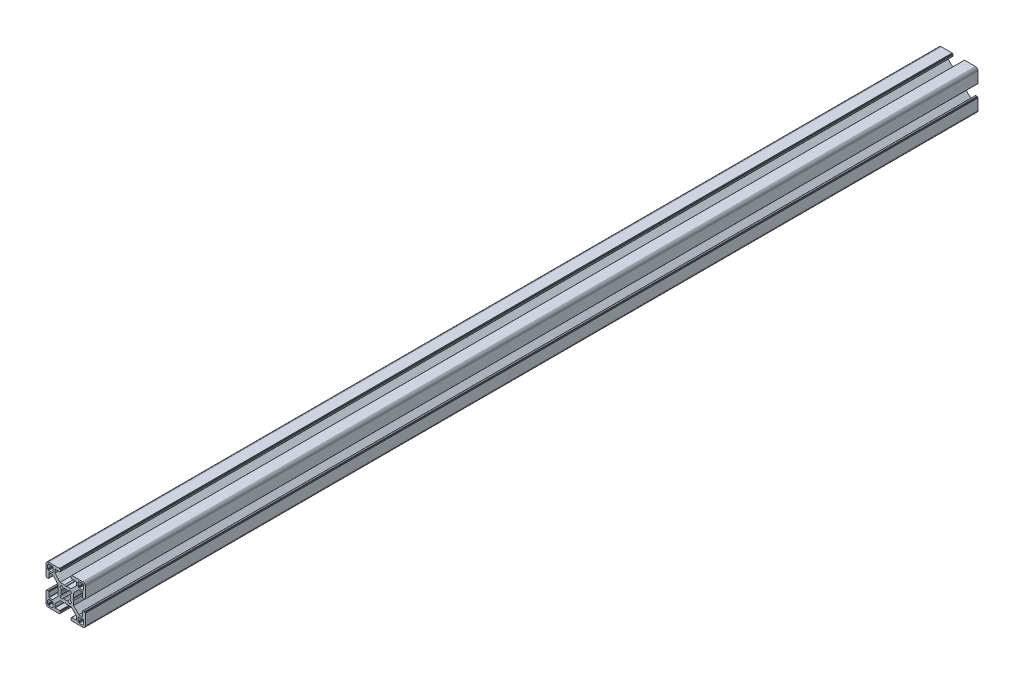
SolidWorks part; units mm, degrees
ref_plane "Front Plane" through (0, 0, 0) normal (0, 0, 1) x (1, 0, 0)
ref_plane "Top Plane" through (0, 0, 0) normal (0, 1, 0) x (1, 0, 0)
ref_plane "Right Plane" through (0, 0, 0) normal (1, 0, 0) x (0, 0, -1)
ref_plane "Plane1" through (0, 0, 0) normal (0, 0, 1) x (1, 0, 0)
sketch "Sketch1" plane through (0, 0, 0) normal (0, 0, 1) x (1, 0, 0)
  line L0 (28.3473, 29.9696) -> (28, 30)
  line L1 (28, 30) -> (19.75, 30)
  line L2 (19.75, 30) -> (19.7153, 29.997)
  line L3 (19.7153, 29.997) -> (19.6816, 29.9879)
  line L4 (19.6816, 29.9879) -> (19.65, 29.9732)
  line L5 (19.65, 29.9732) -> (19.6214, 29.9532)
  line L6 (19.6214, 29.9532) -> (19.5968, 29.9286)
  line L7 (19.5968, 29.9286) -> (19.5768, 29.9)
  line L8 (19.5768, 29.9) -> (19.5621, 29.8684)
  line L9 (19.5621, 29.8684) -> (19.553, 29.8347)
  line L10 (19.553, 29.8347) -> (19.55, 29.8)
  line L11 (19.55, 29.8) -> (19.55, 29.7)
  line L12 (19.55, 29.7) -> (19.547, 29.6653)
  line L13 (19.547, 29.6653) -> (19.5379, 29.6316)
  line L14 (19.5379, 29.6316) -> (19.5232, 29.6)
  line L15 (19.5232, 29.6) -> (19.5032, 29.5714)
  line L16 (19.5032, 29.5714) -> (19.4786, 29.5468)
  line L17 (19.4786, 29.5468) -> (19.45, 29.5268)
  line L18 (19.45, 29.5268) -> (19.4184, 29.5121)
  line L19 (19.4184, 29.5121) -> (19.3847, 29.503)
  line L20 (19.3847, 29.503) -> (19.35, 29.5)
  line L21 (19.35, 29.5) -> (19.25, 29.5)
  line L22 (19.25, 29.5) -> (19.2153, 29.497)
  line L23 (19.2153, 29.497) -> (19.1816, 29.4879)
  line L24 (19.1816, 29.4879) -> (19.15, 29.4732)
  line L25 (19.15, 29.4732) -> (19.1214, 29.4532)
  line L26 (19.1214, 29.4532) -> (19.0968, 29.4286)
  line L27 (19.0968, 29.4286) -> (19.0768, 29.4)
  line L28 (19.0768, 29.4) -> (19.0621, 29.3684)
  line L29 (19.0621, 29.3684) -> (19.053, 29.3347)
  line L30 (19.053, 29.3347) -> (19.05, 29.3)
  line L31 (19.05, 29.3) -> (19.05, 28.4)
  line L32 (19.05, 28.4) -> (19.0591, 28.2958)
  line L33 (19.0591, 28.2958) -> (19.0862, 28.1948)
  line L34 (19.0862, 28.1948) -> (19.1304, 28.1)
  line L35 (19.1304, 28.1) -> (19.1904, 28.0143)
  line L36 (19.1904, 28.0143) -> (19.2643, 27.9404)
  line L37 (19.2643, 27.9404) -> (19.35, 27.8804)
  line L38 (19.35, 27.8804) -> (19.4448, 27.8362)
  line L39 (19.4448, 27.8362) -> (19.5458, 27.8091)
  line L40 (19.5458, 27.8091) -> (19.65, 27.8)
  line L41 (19.65, 27.8) -> (23.05, 27.8)
  line L42 (23.05, 27.8) -> (23.0847, 27.7969)
  line L43 (23.0847, 27.7969) -> (23.1184, 27.7879)
  line L44 (23.1184, 27.7879) -> (23.15, 27.7732)
  line L45 (23.15, 27.7732) -> (23.1786, 27.7532)
  line L46 (23.1786, 27.7532) -> (23.2032, 27.7285)
  line L47 (23.2032, 27.7285) -> (23.2232, 27.7)
  line L48 (23.2232, 27.7) -> (23.2379, 27.6684)
  line L49 (23.2379, 27.6684) -> (23.247, 27.6347)
  line L50 (23.247, 27.6347) -> (23.25, 27.6)
  line L51 (23.25, 27.6) -> (23.25, 25.05)
  line L52 (23.25, 25.05) -> (19.2045, 21)
  line L53 (19.2045, 21) -> (15.9, 21)
  line L54 (15.9, 21) -> (15, 20.4848)
  line L55 (15, 20.4848) -> (14.1, 21)
  line L56 (14.1, 21) -> (10.7955, 21)
  line L57 (10.7955, 21) -> (7.9973, 23.8013)
  line L58 (7.9973, 23.8013) -> (6.75, 25.05)
  line L59 (6.75, 25.05) -> (6.75, 27.6)
  line L60 (6.75, 27.6) -> (6.753, 27.6347)
  line L61 (6.753, 27.6347) -> (6.7621, 27.6684)
  line L62 (6.7621, 27.6684) -> (6.7768, 27.7)
  line L63 (6.7768, 27.7) -> (6.7968, 27.7285)
  line L64 (6.7968, 27.7285) -> (6.8215, 27.7532)
  line L65 (6.8215, 27.7532) -> (6.85, 27.7732)
  line L66 (6.85, 27.7732) -> (6.8816, 27.7879)
  line L67 (6.8816, 27.7879) -> (6.9153, 27.7969)
  line L68 (6.9153, 27.7969) -> (6.95, 27.8)
  line L69 (6.95, 27.8) -> (10.35, 27.8)
  line L70 (10.35, 27.8) -> (10.4542, 27.8091)
  line L71 (10.4542, 27.8091) -> (10.5552, 27.8362)
  line L72 (10.5552, 27.8362) -> (10.65, 27.8804)
  line L73 (10.65, 27.8804) -> (10.7357, 27.9404)
  line L74 (10.7357, 27.9404) -> (10.8096, 28.0143)
  line L75 (10.8096, 28.0143) -> (10.8696, 28.1)
  line L76 (10.8696, 28.1) -> (10.9138, 28.1948)
  line L77 (10.9138, 28.1948) -> (10.9409, 28.2958)
  line L78 (10.9409, 28.2958) -> (10.95, 28.4)
  line L79 (10.95, 28.4) -> (10.95, 29.3)
  line L80 (10.95, 29.3) -> (10.947, 29.3347)
  line L81 (10.947, 29.3347) -> (10.938, 29.3684)
  line L82 (10.938, 29.3684) -> (10.9232, 29.4)
  line L83 (10.9232, 29.4) -> (10.9032, 29.4286)
  line L84 (10.9032, 29.4286) -> (10.8786, 29.4532)
  line L85 (10.8786, 29.4532) -> (10.85, 29.4732)
  line L86 (10.85, 29.4732) -> (10.8184, 29.4879)
  line L87 (10.8184, 29.4879) -> (10.7847, 29.497)
  line L88 (10.7847, 29.497) -> (10.75, 29.5)
  line L89 (10.75, 29.5) -> (10.65, 29.5)
  line L90 (10.65, 29.5) -> (10.6153, 29.503)
  line L91 (10.6153, 29.503) -> (10.5816, 29.5121)
  line L92 (10.5816, 29.5121) -> (10.55, 29.5268)
  line L93 (10.55, 29.5268) -> (10.5214, 29.5468)
  line L94 (10.5214, 29.5468) -> (10.4968, 29.5714)
  line L95 (10.4968, 29.5714) -> (10.4768, 29.6)
  line L96 (10.4768, 29.6) -> (10.4621, 29.6316)
  line L97 (10.4621, 29.6316) -> (10.453, 29.6653)
  line L98 (10.453, 29.6653) -> (10.45, 29.7)
  line L99 (10.45, 29.7) -> (10.45, 29.8)
  line L100 (10.45, 29.8) -> (10.447, 29.8347)
  line L101 (10.447, 29.8347) -> (10.4379, 29.8684)
  line L102 (10.4379, 29.8684) -> (10.4232, 29.9)
  line L103 (10.4232, 29.9) -> (10.4032, 29.9286)
  line L104 (10.4032, 29.9286) -> (10.3786, 29.9532)
  line L105 (10.3786, 29.9532) -> (10.35, 29.9732)
  line L106 (10.35, 29.9732) -> (10.3184, 29.9879)
  line L107 (10.3184, 29.9879) -> (10.2847, 29.997)
  line L108 (10.2847, 29.997) -> (10.25, 30)
  line L109 (10.25, 30) -> (2, 30)
  line L110 (2, 30) -> (1.6527, 29.9696)
  line L111 (1.6527, 29.9696) -> (1.316, 29.8794)
  line L112 (1.316, 29.8794) -> (1, 29.7321)
  line L113 (1, 29.7321) -> (0.7144, 29.5321)
  line L114 (0.7144, 29.5321) -> (0.4679, 29.2856)
  line L115 (0.4679, 29.2856) -> (0.2679, 29)
  line L116 (0.2679, 29) -> (0.1206, 28.684)
  line L117 (0.1206, 28.684) -> (0.0304, 28.3473)
  line L118 (0.0304, 28.3473) -> (0, 28)
  line L119 (0, 28) -> (0, 19.75)
  line L120 (0, 19.75) -> (0.003, 19.7153)
  line L121 (0.003, 19.7153) -> (0.0121, 19.6816)
  line L122 (0.0121, 19.6816) -> (0.0268, 19.65)
  line L123 (0.0268, 19.65) -> (0.0468, 19.6214)
  line L124 (0.0468, 19.6214) -> (0.0714, 19.5968)
  line L125 (0.0714, 19.5968) -> (0.1, 19.5768)
  line L126 (0.1, 19.5768) -> (0.1316, 19.5621)
  line L127 (0.1316, 19.5621) -> (0.1653, 19.553)
  line L128 (0.1653, 19.553) -> (0.2, 19.55)
  line L129 (0.2, 19.55) -> (0.3, 19.55)
  line L130 (0.3, 19.55) -> (0.3347, 19.547)
  line L131 (0.3347, 19.547) -> (0.3684, 19.5379)
  line L132 (0.3684, 19.5379) -> (0.4, 19.5232)
  line L133 (0.4, 19.5232) -> (0.4286, 19.5032)
  line L134 (0.4286, 19.5032) -> (0.4532, 19.4786)
  line L135 (0.4532, 19.4786) -> (0.4732, 19.45)
  line L136 (0.4732, 19.45) -> (0.4879, 19.4184)
  line L137 (0.4879, 19.4184) -> (0.497, 19.3847)
  line L138 (0.497, 19.3847) -> (0.5, 19.35)
  line L139 (0.5, 19.35) -> (0.5, 19.25)
  line L140 (0.5, 19.25) -> (0.503, 19.2153)
  line L141 (0.503, 19.2153) -> (0.5121, 19.1816)
  line L142 (0.5121, 19.1816) -> (0.5268, 19.15)
  line L143 (0.5268, 19.15) -> (0.5468, 19.1214)
  line L144 (0.5468, 19.1214) -> (0.5714, 19.0968)
  line L145 (0.5714, 19.0968) -> (0.6, 19.0768)
  line L146 (0.6, 19.0768) -> (0.6316, 19.0621)
  line L147 (0.6316, 19.0621) -> (0.6653, 19.053)
  line L148 (0.6653, 19.053) -> (0.7, 19.05)
  line L149 (0.7, 19.05) -> (1.6, 19.05)
  line L150 (1.6, 19.05) -> (1.7042, 19.0591)
  line L151 (1.7042, 19.0591) -> (1.8052, 19.0862)
  line L152 (1.8052, 19.0862) -> (1.9, 19.1304)
  line L153 (1.9, 19.1304) -> (1.9857, 19.1904)
  line L154 (1.9857, 19.1904) -> (2.0596, 19.2643)
  line L155 (2.0596, 19.2643) -> (2.1196, 19.35)
  line L156 (2.1196, 19.35) -> (2.1638, 19.4448)
  line L157 (2.1638, 19.4448) -> (2.1909, 19.5458)
  line L158 (2.1909, 19.5458) -> (2.2, 19.65)
  line L159 (2.2, 19.65) -> (2.2, 23.05)
  line L160 (2.2, 23.05) -> (2.203, 23.0847)
  line L161 (2.203, 23.0847) -> (2.2121, 23.1184)
  line L162 (2.2121, 23.1184) -> (2.2268, 23.15)
  line L163 (2.2268, 23.15) -> (2.2468, 23.1786)
  line L164 (2.2468, 23.1786) -> (2.2714, 23.2032)
  line L165 (2.2714, 23.2032) -> (2.3, 23.2232)
  line L166 (2.3, 23.2232) -> (2.3316, 23.2379)
  line L167 (2.3316, 23.2379) -> (2.3653, 23.247)
  line L168 (2.3653, 23.247) -> (2.4, 23.25)
  line L169 (2.4, 23.25) -> (4.95, 23.25)
  line L170 (4.95, 23.25) -> (7.9973, 20.2027)
  line L171 (7.9973, 20.2027) -> (8.9955, 19.2045)
  line L172 (8.9955, 19.2045) -> (8.9955, 15.9)
  line L173 (8.9955, 15.9) -> (9.5151, 15)
  line L174 (9.5151, 15) -> (8.9955, 14.1)
  line L175 (8.9955, 14.1) -> (8.9955, 10.7955)
  line L176 (8.9955, 10.7955) -> (4.95, 6.75)
  line L177 (4.95, 6.75) -> (2.4, 6.75)
  line L178 (2.4, 6.75) -> (2.3653, 6.753)
  line L179 (2.3653, 6.753) -> (2.3316, 6.7621)
  line L180 (2.3316, 6.7621) -> (2.3, 6.7768)
  line L181 (2.3, 6.7768) -> (2.2714, 6.7968)
  line L182 (2.2714, 6.7968) -> (2.2468, 6.8214)
  line L183 (2.2468, 6.8214) -> (2.2268, 6.85)
  line L184 (2.2268, 6.85) -> (2.2121, 6.8816)
  line L185 (2.2121, 6.8816) -> (2.203, 6.9153)
  line L186 (2.203, 6.9153) -> (2.2, 6.95)
  line L187 (2.2, 6.95) -> (2.2, 10.35)
  line L188 (2.2, 10.35) -> (2.1909, 10.4542)
  line L189 (2.1909, 10.4542) -> (2.1638, 10.5552)
  line L190 (2.1638, 10.5552) -> (2.1196, 10.65)
  line L191 (2.1196, 10.65) -> (2.0596, 10.7357)
  line L192 (2.0596, 10.7357) -> (1.9857, 10.8096)
  line L193 (1.9857, 10.8096) -> (1.9, 10.8696)
  line L194 (1.9, 10.8696) -> (1.8052, 10.9138)
  line L195 (1.8052, 10.9138) -> (1.7042, 10.9409)
  line L196 (1.7042, 10.9409) -> (1.6, 10.95)
  line L197 (1.6, 10.95) -> (0.7, 10.95)
  line L198 (0.7, 10.95) -> (0.6653, 10.9469)
  line L199 (0.6653, 10.9469) -> (0.6316, 10.9379)
  line L200 (0.6316, 10.9379) -> (0.6, 10.9232)
  line L201 (0.6, 10.9232) -> (0.5715, 10.9032)
  line L202 (0.5715, 10.9032) -> (0.5468, 10.8785)
  line L203 (0.5468, 10.8785) -> (0.5268, 10.85)
  line L204 (0.5268, 10.85) -> (0.5121, 10.8184)
  line L205 (0.5121, 10.8184) -> (0.503, 10.7847)
  line L206 (0.503, 10.7847) -> (0.5, 10.75)
  line L207 (0.5, 10.75) -> (0.5, 10.65)
  line L208 (0.5, 10.65) -> (0.497, 10.6153)
  line L209 (0.497, 10.6153) -> (0.4879, 10.5816)
  line L210 (0.4879, 10.5816) -> (0.4732, 10.55)
  line L211 (0.4732, 10.55) -> (0.4532, 10.5214)
  line L212 (0.4532, 10.5214) -> (0.4286, 10.4968)
  line L213 (0.4286, 10.4968) -> (0.4, 10.4768)
  line L214 (0.4, 10.4768) -> (0.3684, 10.4621)
  line L215 (0.3684, 10.4621) -> (0.3347, 10.453)
  line L216 (0.3347, 10.453) -> (0.3, 10.45)
  line L217 (0.3, 10.45) -> (0.2, 10.45)
  line L218 (0.2, 10.45) -> (0.1653, 10.447)
  line L219 (0.1653, 10.447) -> (0.1316, 10.4379)
  line L220 (0.1316, 10.4379) -> (0.1, 10.4232)
  line L221 (0.1, 10.4232) -> (0.0714, 10.4032)
  line L222 (0.0714, 10.4032) -> (0.0468, 10.3786)
  line L223 (0.0468, 10.3786) -> (0.0268, 10.35)
  line L224 (0.0268, 10.35) -> (0.0121, 10.3184)
  line L225 (0.0121, 10.3184) -> (0.003, 10.2847)
  line L226 (0.003, 10.2847) -> (0, 10.25)
  line L227 (0, 10.25) -> (0, 2)
  line L228 (0, 2) -> (0.0304, 1.6527)
  line L229 (0.0304, 1.6527) -> (0.1206, 1.316)
  line L230 (0.1206, 1.316) -> (0.2679, 1)
  line L231 (0.2679, 1) -> (0.4679, 0.7144)
  line L232 (0.4679, 0.7144) -> (0.7144, 0.4679)
  line L233 (0.7144, 0.4679) -> (1, 0.2679)
  line L234 (1, 0.2679) -> (1.316, 0.1206)
  line L235 (1.316, 0.1206) -> (1.6527, 0.0304)
  line L236 (1.6527, 0.0304) -> (2, 0)
  line L237 (2, 0) -> (10.25, 0)
  line L238 (10.25, 0) -> (10.2847, 0.003)
  line L239 (10.2847, 0.003) -> (10.3184, 0.0121)
  line L240 (10.3184, 0.0121) -> (10.35, 0.0268)
  line L241 (10.35, 0.0268) -> (10.3786, 0.0468)
  line L242 (10.3786, 0.0468) -> (10.4032, 0.0714)
  line L243 (10.4032, 0.0714) -> (10.4232, 0.1)
  line L244 (10.4232, 0.1) -> (10.4379, 0.1316)
  line L245 (10.4379, 0.1316) -> (10.447, 0.1653)
  line L246 (10.447, 0.1653) -> (10.45, 0.2)
  line L247 (10.45, 0.2) -> (10.45, 0.3)
  line L248 (10.45, 0.3) -> (10.453, 0.3347)
  line L249 (10.453, 0.3347) -> (10.4621, 0.3684)
  line L250 (10.4621, 0.3684) -> (10.4768, 0.4)
  line L251 (10.4768, 0.4) -> (10.4968, 0.4286)
  line L252 (10.4968, 0.4286) -> (10.5214, 0.4532)
  line L253 (10.5214, 0.4532) -> (10.55, 0.4732)
  line L254 (10.55, 0.4732) -> (10.5816, 0.4879)
  line L255 (10.5816, 0.4879) -> (10.6153, 0.497)
  line L256 (10.6153, 0.497) -> (10.65, 0.5)
  line L257 (10.65, 0.5) -> (10.75, 0.5)
  line L258 (10.75, 0.5) -> (10.7847, 0.503)
  line L259 (10.7847, 0.503) -> (10.8184, 0.5121)
  line L260 (10.8184, 0.5121) -> (10.85, 0.5268)
  line L261 (10.85, 0.5268) -> (10.8785, 0.5468)
  line L262 (10.8785, 0.5468) -> (10.9032, 0.5715)
  line L263 (10.9032, 0.5715) -> (10.9232, 0.6)
  line L264 (10.9232, 0.6) -> (10.9379, 0.6316)
  line L265 (10.9379, 0.6316) -> (10.9469, 0.6653)
  line L266 (10.9469, 0.6653) -> (10.95, 0.7)
  line L267 (10.95, 0.7) -> (10.95, 1.6)
  line L268 (10.95, 1.6) -> (10.9409, 1.7042)
  line L269 (10.9409, 1.7042) -> (10.9138, 1.8052)
  line L270 (10.9138, 1.8052) -> (10.8696, 1.9)
  line L271 (10.8696, 1.9) -> (10.8096, 1.9857)
  line L272 (10.8096, 1.9857) -> (10.7357, 2.0596)
  line L273 (10.7357, 2.0596) -> (10.65, 2.1196)
  line L274 (10.65, 2.1196) -> (10.5552, 2.1638)
  line L275 (10.5552, 2.1638) -> (10.4542, 2.1909)
  line L276 (10.4542, 2.1909) -> (10.35, 2.2)
  line L277 (10.35, 2.2) -> (6.95, 2.2)
  line L278 (6.95, 2.2) -> (6.9153, 2.203)
  line L279 (6.9153, 2.203) -> (6.8816, 2.212)
  line L280 (6.8816, 2.212) -> (6.85, 2.2268)
  line L281 (6.85, 2.2268) -> (6.8215, 2.2468)
  line L282 (6.8215, 2.2468) -> (6.7968, 2.2714)
  line L283 (6.7968, 2.2714) -> (6.7768, 2.3)
  line L284 (6.7768, 2.3) -> (6.7621, 2.3316)
  line L285 (6.7621, 2.3316) -> (6.753, 2.3653)
  line L286 (6.753, 2.3653) -> (6.75, 2.4)
  line L287 (6.75, 2.4) -> (6.75, 4.95)
  line L288 (6.75, 4.95) -> (9.7875, 7.9908)
  line L289 (9.7875, 7.9908) -> (10.7955, 9)
  line L290 (10.7955, 9) -> (14.1, 9)
  line L291 (14.1, 9) -> (15, 9.5151)
  line L292 (15, 9.5151) -> (15.9, 9)
  line L293 (15.9, 9) -> (19.2045, 9)
  line L294 (19.2045, 9) -> (20.2126, 7.9908)
  line L295 (20.2126, 7.9908) -> (23.25, 4.95)
  line L296 (23.25, 4.95) -> (23.25, 2.4)
  line L297 (23.25, 2.4) -> (23.247, 2.3653)
  line L298 (23.247, 2.3653) -> (23.2379, 2.3316)
  line L299 (23.2379, 2.3316) -> (23.2232, 2.3)
  line L300 (23.2232, 2.3) -> (23.2032, 2.2714)
  line L301 (23.2032, 2.2714) -> (23.1786, 2.2468)
  line L302 (23.1786, 2.2468) -> (23.15, 2.2268)
  line L303 (23.15, 2.2268) -> (23.1184, 2.212)
  line L304 (23.1184, 2.212) -> (23.0847, 2.203)
  line L305 (23.0847, 2.203) -> (23.05, 2.2)
  line L306 (23.05, 2.2) -> (19.65, 2.2)
  line L307 (19.65, 2.2) -> (19.5458, 2.1909)
  line L308 (19.5458, 2.1909) -> (19.4448, 2.1638)
  line L309 (19.4448, 2.1638) -> (19.35, 2.1196)
  line L310 (19.35, 2.1196) -> (19.2643, 2.0596)
  line L311 (19.2643, 2.0596) -> (19.1904, 1.9857)
  line L312 (19.1904, 1.9857) -> (19.1304, 1.9)
  line L313 (19.1304, 1.9) -> (19.0862, 1.8052)
  line L314 (19.0862, 1.8052) -> (19.0591, 1.7042)
  line L315 (19.0591, 1.7042) -> (19.05, 1.6)
  line L316 (19.05, 1.6) -> (19.05, 0.7)
  line L317 (19.05, 0.7) -> (19.053, 0.6653)
  line L318 (19.053, 0.6653) -> (19.0621, 0.6316)
  line L319 (19.0621, 0.6316) -> (19.0768, 0.6)
  line L320 (19.0768, 0.6) -> (19.0968, 0.5714)
  line L321 (19.0968, 0.5714) -> (19.1214, 0.5468)
  line L322 (19.1214, 0.5468) -> (19.15, 0.5268)
  line L323 (19.15, 0.5268) -> (19.1816, 0.5121)
  line L324 (19.1816, 0.5121) -> (19.2153, 0.503)
  line L325 (19.2153, 0.503) -> (19.25, 0.5)
  line L326 (19.25, 0.5) -> (19.35, 0.5)
  line L327 (19.35, 0.5) -> (19.3847, 0.497)
  line L328 (19.3847, 0.497) -> (19.4184, 0.4879)
  line L329 (19.4184, 0.4879) -> (19.45, 0.4732)
  line L330 (19.45, 0.4732) -> (19.4786, 0.4532)
  line L331 (19.4786, 0.4532) -> (19.5032, 0.4286)
  line L332 (19.5032, 0.4286) -> (19.5232, 0.4)
  line L333 (19.5232, 0.4) -> (19.5379, 0.3684)
  line L334 (19.5379, 0.3684) -> (19.547, 0.3347)
  line L335 (19.547, 0.3347) -> (19.55, 0.3)
  line L336 (19.55, 0.3) -> (19.55, 0.2)
  line L337 (19.55, 0.2) -> (19.553, 0.1653)
  line L338 (19.553, 0.1653) -> (19.5621, 0.1316)
  line L339 (19.5621, 0.1316) -> (19.5768, 0.1)
  line L340 (19.5768, 0.1) -> (19.5968, 0.0714)
  line L341 (19.5968, 0.0714) -> (19.6214, 0.0468)
  line L342 (19.6214, 0.0468) -> (19.65, 0.0268)
  line L343 (19.65, 0.0268) -> (19.6816, 0.0121)
  line L344 (19.6816, 0.0121) -> (19.7153, 0.003)
  line L345 (19.7153, 0.003) -> (19.75, 0)
  line L346 (19.75, 0) -> (28, 0)
  line L347 (28, 0) -> (28.3473, 0.0304)
  line L348 (28.3473, 0.0304) -> (28.684, 0.1206)
  line L349 (28.684, 0.1206) -> (29, 0.2679)
  line L350 (29, 0.2679) -> (29.2856, 0.4679)
  line L351 (29.2856, 0.4679) -> (29.5321, 0.7144)
  line L352 (29.5321, 0.7144) -> (29.7321, 1)
  line L353 (29.7321, 1) -> (29.8794, 1.316)
  line L354 (29.8794, 1.316) -> (29.9696, 1.6527)
  line L355 (29.9696, 1.6527) -> (30, 2)
  line L356 (30, 2) -> (30, 10.25)
  line L357 (30, 10.25) -> (29.997, 10.2847)
  line L358 (29.997, 10.2847) -> (29.988, 10.3184)
  line L359 (29.988, 10.3184) -> (29.9732, 10.35)
  line L360 (29.9732, 10.35) -> (29.9532, 10.3785)
  line L361 (29.9532, 10.3785) -> (29.9286, 10.4032)
  line L362 (29.9286, 10.4032) -> (29.9, 10.4232)
  line L363 (29.9, 10.4232) -> (29.8684, 10.4379)
  line L364 (29.8684, 10.4379) -> (29.8347, 10.447)
  line L365 (29.8347, 10.447) -> (29.8, 10.45)
  line L366 (29.8, 10.45) -> (29.7, 10.45)
  line L367 (29.7, 10.45) -> (29.6649, 10.4534)
  line L368 (29.6649, 10.4534) -> (29.6312, 10.4624)
  line L369 (29.6312, 10.4624) -> (29.5996, 10.4772)
  line L370 (29.5996, 10.4772) -> (29.5711, 10.4972)
  line L371 (29.5711, 10.4972) -> (29.5464, 10.5218)
  line L372 (29.5464, 10.5218) -> (29.5264, 10.5504)
  line L373 (29.5264, 10.5504) -> (29.5117, 10.582)
  line L374 (29.5117, 10.582) -> (29.5027, 10.6156)
  line L375 (29.5027, 10.6156) -> (29.4996, 10.6504)
  line L376 (29.4996, 10.6504) -> (29.4996, 10.7504)
  line L377 (29.4996, 10.7504) -> (29.497, 10.7847)
  line L378 (29.497, 10.7847) -> (29.4879, 10.8184)
  line L379 (29.4879, 10.8184) -> (29.4732, 10.85)
  line L380 (29.4732, 10.85) -> (29.4532, 10.8785)
  line L381 (29.4532, 10.8785) -> (29.4286, 10.9032)
  line L382 (29.4286, 10.9032) -> (29.4, 10.9232)
  line L383 (29.4, 10.9232) -> (29.3684, 10.9379)
  line L384 (29.3684, 10.9379) -> (29.3347, 10.9469)
  line L385 (29.3347, 10.9469) -> (29.3, 10.95)
  line L386 (29.3, 10.95) -> (28.4, 10.95)
  line L387 (28.4, 10.95) -> (28.2958, 10.9409)
  line L388 (28.2958, 10.9409) -> (28.1948, 10.9138)
  line L389 (28.1948, 10.9138) -> (28.1, 10.8696)
  line L390 (28.1, 10.8696) -> (28.0143, 10.8096)
  line L391 (28.0143, 10.8096) -> (27.9404, 10.7357)
  line L392 (27.9404, 10.7357) -> (27.8804, 10.65)
  line L393 (27.8804, 10.65) -> (27.8362, 10.5552)
  line L394 (27.8362, 10.5552) -> (27.8091, 10.4542)
  line L395 (27.8091, 10.4542) -> (27.8, 10.35)
  line L396 (27.8, 10.35) -> (27.8, 6.95)
  line L397 (27.8, 6.95) -> (27.797, 6.9153)
  line L398 (27.797, 6.9153) -> (27.7879, 6.8816)
  line L399 (27.7879, 6.8816) -> (27.7732, 6.85)
  line L400 (27.7732, 6.85) -> (27.7532, 6.8214)
  line L401 (27.7532, 6.8214) -> (27.7286, 6.7968)
  line L402 (27.7286, 6.7968) -> (27.7, 6.7768)
  line L403 (27.7, 6.7768) -> (27.6684, 6.7621)
  line L404 (27.6684, 6.7621) -> (27.6347, 6.753)
  line L405 (27.6347, 6.753) -> (27.6, 6.75)
  line L406 (27.6, 6.75) -> (25.05, 6.75)
  line L407 (25.05, 6.75) -> (23.8092, 7.9908)
  line L408 (23.8092, 7.9908) -> (21.0045, 10.7955)
  line L409 (21.0045, 10.7955) -> (21.0045, 14.1)
  line L410 (21.0045, 14.1) -> (20.4849, 15)
  line L411 (20.4849, 15) -> (21.0045, 15.9)
  line L412 (21.0045, 15.9) -> (21.0045, 19.2045)
  line L413 (21.0045, 19.2045) -> (25.05, 23.25)
  line L414 (25.05, 23.25) -> (27.6, 23.25)
  line L415 (27.6, 23.25) -> (27.6347, 23.247)
  line L416 (27.6347, 23.247) -> (27.6684, 23.2379)
  line L417 (27.6684, 23.2379) -> (27.7, 23.2232)
  line L418 (27.7, 23.2232) -> (27.7286, 23.2032)
  line L419 (27.7286, 23.2032) -> (27.7532, 23.1786)
  line L420 (27.7532, 23.1786) -> (27.7732, 23.15)
  line L421 (27.7732, 23.15) -> (27.7879, 23.1184)
  line L422 (27.7879, 23.1184) -> (27.797, 23.0847)
  line L423 (27.797, 23.0847) -> (27.8, 23.05)
  line L424 (27.8, 23.05) -> (27.8, 19.65)
  line L425 (27.8, 19.65) -> (27.8091, 19.5458)
  line L426 (27.8091, 19.5458) -> (27.8362, 19.4448)
  line L427 (27.8362, 19.4448) -> (27.8804, 19.35)
  line L428 (27.8804, 19.35) -> (27.9404, 19.2643)
  line L429 (27.9404, 19.2643) -> (28.0143, 19.1904)
  line L430 (28.0143, 19.1904) -> (28.1, 19.1304)
  line L431 (28.1, 19.1304) -> (28.1948, 19.0862)
  line L432 (28.1948, 19.0862) -> (28.2958, 19.0591)
  line L433 (28.2958, 19.0591) -> (28.4, 19.05)
  line L434 (28.4, 19.05) -> (29.3, 19.05)
  line L435 (29.3, 19.05) -> (29.3347, 19.053)
  line L436 (29.3347, 19.053) -> (29.3684, 19.0621)
  line L437 (29.3684, 19.0621) -> (29.4, 19.0768)
  line L438 (29.4, 19.0768) -> (29.4282, 19.0971)
  line L439 (29.4282, 19.0971) -> (29.4528, 19.1218)
  line L440 (29.4528, 19.1218) -> (29.4728, 19.1504)
  line L441 (29.4728, 19.1504) -> (29.4876, 19.182)
  line L442 (29.4876, 19.182) -> (29.4966, 19.2156)
  line L443 (29.4966, 19.2156) -> (29.4996, 19.2504)
  line L444 (29.4996, 19.2504) -> (29.4996, 19.3504)
  line L445 (29.4996, 19.3504) -> (29.5027, 19.3851)
  line L446 (29.5027, 19.3851) -> (29.5117, 19.4188)
  line L447 (29.5117, 19.4188) -> (29.5264, 19.4504)
  line L448 (29.5264, 19.4504) -> (29.5464, 19.4789)
  line L449 (29.5464, 19.4789) -> (29.5711, 19.5036)
  line L450 (29.5711, 19.5036) -> (29.5996, 19.5236)
  line L451 (29.5996, 19.5236) -> (29.6312, 19.5383)
  line L452 (29.6312, 19.5383) -> (29.6649, 19.5473)
  line L453 (29.6649, 19.5473) -> (29.7, 19.55)
  line L454 (29.7, 19.55) -> (29.8, 19.55)
  line L455 (29.8, 19.55) -> (29.8347, 19.553)
  line L456 (29.8347, 19.553) -> (29.8684, 19.5621)
  line L457 (29.8684, 19.5621) -> (29.9, 19.5768)
  line L458 (29.9, 19.5768) -> (29.9286, 19.5968)
  line L459 (29.9286, 19.5968) -> (29.9532, 19.6214)
  line L460 (29.9532, 19.6214) -> (29.9732, 19.65)
  line L461 (29.9732, 19.65) -> (29.9879, 19.6816)
  line L462 (29.9879, 19.6816) -> (29.997, 19.7153)
  line L463 (29.997, 19.7153) -> (30, 19.75)
  line L464 (30, 19.75) -> (30, 28)
  line L465 (30, 28) -> (29.9696, 28.3473)
  line L466 (29.9696, 28.3473) -> (29.8794, 28.684)
  line L467 (29.8794, 28.684) -> (29.7321, 29)
  line L468 (29.7321, 29) -> (29.5321, 29.2856)
  line L469 (29.5321, 29.2856) -> (29.2856, 29.5321)
  line L470 (29.2856, 29.5321) -> (29, 29.7321)
  line L471 (29, 29.7321) -> (28.684, 29.8794)
  line L472 (28.684, 29.8794) -> (28.3473, 29.9696)
  line L473 (1.3, 25.5) -> (1.3, 27.7)
  line L474 (1.3, 27.7) -> (1.3123, 27.8564)
  line L475 (1.3123, 27.8564) -> (1.3489, 28.009)
  line L476 (1.3489, 28.009) -> (1.409, 28.154)
  line L477 (1.409, 28.154) -> (1.491, 28.2878)
  line L478 (1.491, 28.2878) -> (1.5929, 28.4071)
  line L479 (1.5929, 28.4071) -> (1.7122, 28.509)
  line L480 (1.7122, 28.509) -> (1.846, 28.591)
  line L481 (1.846, 28.591) -> (1.991, 28.6511)
  line L482 (1.991, 28.6511) -> (2.1436, 28.6877)
  line L483 (2.1436, 28.6877) -> (2.3, 28.7)
  line L484 (2.3, 28.7) -> (4.5, 28.7)
  line L485 (4.5, 28.7) -> (4.6564, 28.6877)
  line L486 (4.6564, 28.6877) -> (4.809, 28.6511)
  line L487 (4.809, 28.6511) -> (4.954, 28.591)
  line L488 (4.954, 28.591) -> (5.0878, 28.509)
  line L489 (5.0878, 28.509) -> (5.2071, 28.4071)
  line L490 (5.2071, 28.4071) -> (5.309, 28.2878)
  line L491 (5.309, 28.2878) -> (5.391, 28.154)
  line L492 (5.391, 28.154) -> (5.4511, 28.009)
  line L493 (5.4511, 28.009) -> (5.4877, 27.8564)
  line L494 (5.4877, 27.8564) -> (5.5, 27.7)
  line L495 (5.5, 27.7) -> (5.5, 25.5)
  line L496 (5.5, 25.5) -> (5.4877, 25.3436)
  line L497 (5.4877, 25.3436) -> (5.4511, 25.191)
  line L498 (5.4511, 25.191) -> (5.391, 25.046)
  line L499 (5.391, 25.046) -> (5.309, 24.9122)
  line L500 (5.309, 24.9122) -> (5.2071, 24.7929)
  line L501 (5.2071, 24.7929) -> (5.0878, 24.691)
  line L502 (5.0878, 24.691) -> (4.954, 24.609)
  line L503 (4.954, 24.609) -> (4.809, 24.5489)
  line L504 (4.809, 24.5489) -> (4.6564, 24.5123)
  line L505 (4.6564, 24.5123) -> (4.5, 24.5)
  line L506 (4.5, 24.5) -> (2.3, 24.5)
  line L507 (2.3, 24.5) -> (2.1436, 24.5123)
  line L508 (2.1436, 24.5123) -> (1.991, 24.5489)
  line L509 (1.991, 24.5489) -> (1.846, 24.609)
  line L510 (1.846, 24.609) -> (1.7122, 24.691)
  line L511 (1.7122, 24.691) -> (1.5929, 24.7929)
  line L512 (1.5929, 24.7929) -> (1.491, 24.9122)
  line L513 (1.491, 24.9122) -> (1.409, 25.046)
  line L514 (1.409, 25.046) -> (1.3489, 25.191)
  line L515 (1.3489, 25.191) -> (1.3123, 25.3436)
  line L516 (1.3123, 25.3436) -> (1.3, 25.5)
  line L517 (25.3436, 28.6877) -> (25.5, 28.7)
  line L518 (25.5, 28.7) -> (27.7, 28.7)
  line L519 (27.7, 28.7) -> (27.8564, 28.6877)
  line L520 (27.8564, 28.6877) -> (28.009, 28.6511)
  line L521 (28.009, 28.6511) -> (28.154, 28.591)
  line L522 (28.154, 28.591) -> (28.2878, 28.509)
  line L523 (28.2878, 28.509) -> (28.4071, 28.4071)
  line L524 (28.4071, 28.4071) -> (28.509, 28.2878)
  line L525 (28.509, 28.2878) -> (28.591, 28.154)
  line L526 (28.591, 28.154) -> (28.6511, 28.009)
  line L527 (28.6511, 28.009) -> (28.6877, 27.8564)
  line L528 (28.6877, 27.8564) -> (28.7, 27.7)
  line L529 (28.7, 27.7) -> (28.7, 25.5)
  line L530 (28.7, 25.5) -> (28.6877, 25.3436)
  line L531 (28.6877, 25.3436) -> (28.6511, 25.191)
  line L532 (28.6511, 25.191) -> (28.591, 25.046)
  line L533 (28.591, 25.046) -> (28.509, 24.9122)
  line L534 (28.509, 24.9122) -> (28.4071, 24.7929)
  line L535 (28.4071, 24.7929) -> (28.2878, 24.691)
  line L536 (28.2878, 24.691) -> (28.154, 24.609)
  line L537 (28.154, 24.609) -> (28.009, 24.5489)
  line L538 (28.009, 24.5489) -> (27.8564, 24.5123)
  line L539 (27.8564, 24.5123) -> (27.7, 24.5)
  line L540 (27.7, 24.5) -> (25.5, 24.5)
  line L541 (25.5, 24.5) -> (25.3436, 24.5123)
  line L542 (25.3436, 24.5123) -> (25.191, 24.5489)
  line L543 (25.191, 24.5489) -> (25.046, 24.609)
  line L544 (25.046, 24.609) -> (24.9122, 24.691)
  line L545 (24.9122, 24.691) -> (24.7929, 24.7929)
  line L546 (24.7929, 24.7929) -> (24.691, 24.9122)
  line L547 (24.691, 24.9122) -> (24.609, 25.046)
  line L548 (24.609, 25.046) -> (24.5489, 25.191)
  line L549 (24.5489, 25.191) -> (24.5123, 25.3436)
  line L550 (24.5123, 25.3436) -> (24.5, 25.5)
  line L551 (24.5, 25.5) -> (24.5, 27.7)
  line L552 (24.5, 27.7) -> (24.5123, 27.8564)
  line L553 (24.5123, 27.8564) -> (24.5489, 28.009)
  line L554 (24.5489, 28.009) -> (24.609, 28.154)
  line L555 (24.609, 28.154) -> (24.691, 28.2878)
  line L556 (24.691, 28.2878) -> (24.7929, 28.4071)
  line L557 (24.7929, 28.4071) -> (24.9122, 28.509)
  line L558 (24.9122, 28.509) -> (25.046, 28.591)
  line L559 (25.046, 28.591) -> (25.191, 28.6511)
  line L560 (25.191, 28.6511) -> (25.3436, 28.6877)
  line L561 (15, 18.65) -> (15.55, 18.6083)
  line L562 (15.55, 18.6083) -> (16.0875, 18.4842)
  line L563 (16.0875, 18.4842) -> (16.6001, 18.2806)
  line L564 (16.6001, 18.2806) -> (18.1359, 19.5184)
  line L565 (18.1359, 19.5184) -> (18.645, 19.1187)
  line L566 (18.645, 19.1187) -> (19.1036, 18.6621)
  line L567 (19.1036, 18.6621) -> (19.5053, 18.1547)
  line L568 (19.5053, 18.1547) -> (18.2806, 16.6001)
  line L569 (18.2806, 16.6001) -> (18.4842, 16.0875)
  line L570 (18.4842, 16.0875) -> (18.6083, 15.55)
  line L571 (18.6083, 15.55) -> (18.65, 15)
  line L572 (18.65, 15) -> (18.6083, 14.45)
  line L573 (18.6083, 14.45) -> (18.4842, 13.9125)
  line L574 (18.4842, 13.9125) -> (18.2806, 13.3999)
  line L575 (18.2806, 13.3999) -> (19.5053, 11.8453)
  line L576 (19.5053, 11.8453) -> (19.1036, 11.3379)
  line L577 (19.1036, 11.3379) -> (18.645, 10.8813)
  line L578 (18.645, 10.8813) -> (18.1359, 10.4816)
  line L579 (18.1359, 10.4816) -> (16.6001, 11.7194)
  line L580 (16.6001, 11.7194) -> (16.0875, 11.5158)
  line L581 (16.0875, 11.5158) -> (15.55, 11.3917)
  line L582 (15.55, 11.3917) -> (15, 11.35)
  line L583 (15, 11.35) -> (14.45, 11.3917)
  line L584 (14.45, 11.3917) -> (13.9125, 11.5158)
  line L585 (13.9125, 11.5158) -> (13.3999, 11.7194)
  line L586 (13.3999, 11.7194) -> (11.8641, 10.4816)
  line L587 (11.8641, 10.4816) -> (11.355, 10.8813)
  line L588 (11.355, 10.8813) -> (10.8964, 11.3379)
  line L589 (10.8964, 11.3379) -> (10.4947, 11.8453)
  line L590 (10.4947, 11.8453) -> (11.7194, 13.3999)
  line L591 (11.7194, 13.3999) -> (11.5158, 13.9125)
  line L592 (11.5158, 13.9125) -> (11.3917, 14.45)
  line L593 (11.3917, 14.45) -> (11.35, 15)
  line L594 (11.35, 15) -> (11.3917, 15.55)
  line L595 (11.3917, 15.55) -> (11.5158, 16.0875)
  line L596 (11.5158, 16.0875) -> (11.7194, 16.6001)
  line L597 (11.7194, 16.6001) -> (10.4947, 18.1547)
  line L598 (10.4947, 18.1547) -> (10.8964, 18.6621)
  line L599 (10.8964, 18.6621) -> (11.355, 19.1187)
  line L600 (11.355, 19.1187) -> (11.8641, 19.5184)
  line L601 (11.8641, 19.5184) -> (13.3999, 18.2806)
  line L602 (13.3999, 18.2806) -> (13.9125, 18.4842)
  line L603 (13.9125, 18.4842) -> (14.45, 18.6083)
  line L604 (14.45, 18.6083) -> (15, 18.65)
  line L605 (4.5, 1.3) -> (2.3, 1.3)
  line L606 (2.3, 1.3) -> (2.1436, 1.3123)
  line L607 (2.1436, 1.3123) -> (1.991, 1.3489)
  line L608 (1.991, 1.3489) -> (1.846, 1.409)
  line L609 (1.846, 1.409) -> (1.7122, 1.491)
  line L610 (1.7122, 1.491) -> (1.5929, 1.5929)
  line L611 (1.5929, 1.5929) -> (1.491, 1.7122)
  line L612 (1.491, 1.7122) -> (1.409, 1.846)
  line L613 (1.409, 1.846) -> (1.3489, 1.991)
  line L614 (1.3489, 1.991) -> (1.3123, 2.1436)
  line L615 (1.3123, 2.1436) -> (1.3, 2.3)
  line L616 (1.3, 2.3) -> (1.3, 4.5)
  line L617 (1.3, 4.5) -> (1.3123, 4.6564)
  line L618 (1.3123, 4.6564) -> (1.3489, 4.809)
  line L619 (1.3489, 4.809) -> (1.409, 4.954)
  line L620 (1.409, 4.954) -> (1.491, 5.0878)
  line L621 (1.491, 5.0878) -> (1.5929, 5.2071)
  line L622 (1.5929, 5.2071) -> (1.7122, 5.309)
  line L623 (1.7122, 5.309) -> (1.846, 5.391)
  line L624 (1.846, 5.391) -> (1.991, 5.4511)
  line L625 (1.991, 5.4511) -> (2.1436, 5.4877)
  line L626 (2.1436, 5.4877) -> (2.3, 5.5)
  line L627 (2.3, 5.5) -> (4.5, 5.5)
  line L628 (4.5, 5.5) -> (4.6564, 5.4877)
  line L629 (4.6564, 5.4877) -> (4.809, 5.4511)
  line L630 (4.809, 5.4511) -> (4.954, 5.391)
  line L631 (4.954, 5.391) -> (5.0878, 5.309)
  line L632 (5.0878, 5.309) -> (5.2071, 5.2071)
  line L633 (5.2071, 5.2071) -> (5.309, 5.0878)
  line L634 (5.309, 5.0878) -> (5.391, 4.954)
  line L635 (5.391, 4.954) -> (5.4511, 4.809)
  line L636 (5.4511, 4.809) -> (5.4877, 4.6564)
  line L637 (5.4877, 4.6564) -> (5.5, 4.5)
  line L638 (5.5, 4.5) -> (5.5, 2.3)
  line L639 (5.5, 2.3) -> (5.4877, 2.1436)
  line L640 (5.4877, 2.1436) -> (5.4511, 1.991)
  line L641 (5.4511, 1.991) -> (5.391, 1.846)
  line L642 (5.391, 1.846) -> (5.309, 1.7122)
  line L643 (5.309, 1.7122) -> (5.2071, 1.5929)
  line L644 (5.2071, 1.5929) -> (5.0878, 1.491)
  line L645 (5.0878, 1.491) -> (4.954, 1.409)
  line L646 (4.954, 1.409) -> (4.809, 1.3489)
  line L647 (4.809, 1.3489) -> (4.6564, 1.3123)
  line L648 (4.6564, 1.3123) -> (4.5, 1.3)
  line L649 (27.7, 1.3) -> (25.5, 1.3)
  line L650 (25.5, 1.3) -> (25.3436, 1.3123)
  line L651 (25.3436, 1.3123) -> (25.191, 1.3489)
  line L652 (25.191, 1.3489) -> (25.046, 1.409)
  line L653 (25.046, 1.409) -> (24.9122, 1.491)
  line L654 (24.9122, 1.491) -> (24.7929, 1.5929)
  line L655 (24.7929, 1.5929) -> (24.691, 1.7122)
  line L656 (24.691, 1.7122) -> (24.609, 1.846)
  line L657 (24.609, 1.846) -> (24.5489, 1.991)
  line L658 (24.5489, 1.991) -> (24.5123, 2.1436)
  line L659 (24.5123, 2.1436) -> (24.5, 2.3)
  line L660 (24.5, 2.3) -> (24.5, 4.5)
  line L661 (24.5, 4.5) -> (24.5123, 4.6564)
  line L662 (24.5123, 4.6564) -> (24.5489, 4.809)
  line L663 (24.5489, 4.809) -> (24.609, 4.954)
  line L664 (24.609, 4.954) -> (24.691, 5.0878)
  line L665 (24.691, 5.0878) -> (24.7929, 5.2071)
  line L666 (24.7929, 5.2071) -> (24.9122, 5.309)
  line L667 (24.9122, 5.309) -> (25.046, 5.391)
  line L668 (25.046, 5.391) -> (25.191, 5.4511)
  line L669 (25.191, 5.4511) -> (25.3436, 5.4877)
  line L670 (25.3436, 5.4877) -> (25.5, 5.5)
  line L671 (25.5, 5.5) -> (27.7, 5.5)
  line L672 (27.7, 5.5) -> (27.8564, 5.4877)
  line L673 (27.8564, 5.4877) -> (28.009, 5.4511)
  line L674 (28.009, 5.4511) -> (28.154, 5.391)
  line L675 (28.154, 5.391) -> (28.2878, 5.309)
  line L676 (28.2878, 5.309) -> (28.4071, 5.2071)
  line L677 (28.4071, 5.2071) -> (28.509, 5.0878)
  line L678 (28.509, 5.0878) -> (28.591, 4.954)
  line L679 (28.591, 4.954) -> (28.6511, 4.809)
  line L680 (28.6511, 4.809) -> (28.6877, 4.6564)
  line L681 (28.6877, 4.6564) -> (28.7, 4.5)
  line L682 (28.7, 4.5) -> (28.7, 2.3)
  line L683 (28.7, 2.3) -> (28.6877, 2.1436)
  line L684 (28.6877, 2.1436) -> (28.6511, 1.991)
  line L685 (28.6511, 1.991) -> (28.591, 1.846)
  line L686 (28.591, 1.846) -> (28.509, 1.7122)
  line L687 (28.509, 1.7122) -> (28.4071, 1.5929)
  line L688 (28.4071, 1.5929) -> (28.2878, 1.491)
  line L689 (28.2878, 1.491) -> (28.154, 1.409)
  line L690 (28.154, 1.409) -> (28.009, 1.3489)
  line L691 (28.009, 1.3489) -> (27.8564, 1.3123)
  line L692 (27.8564, 1.3123) -> (27.7, 1.3)
extrude "Boss-Extrude1" add sketch "Sketch1" against normal blind 680
